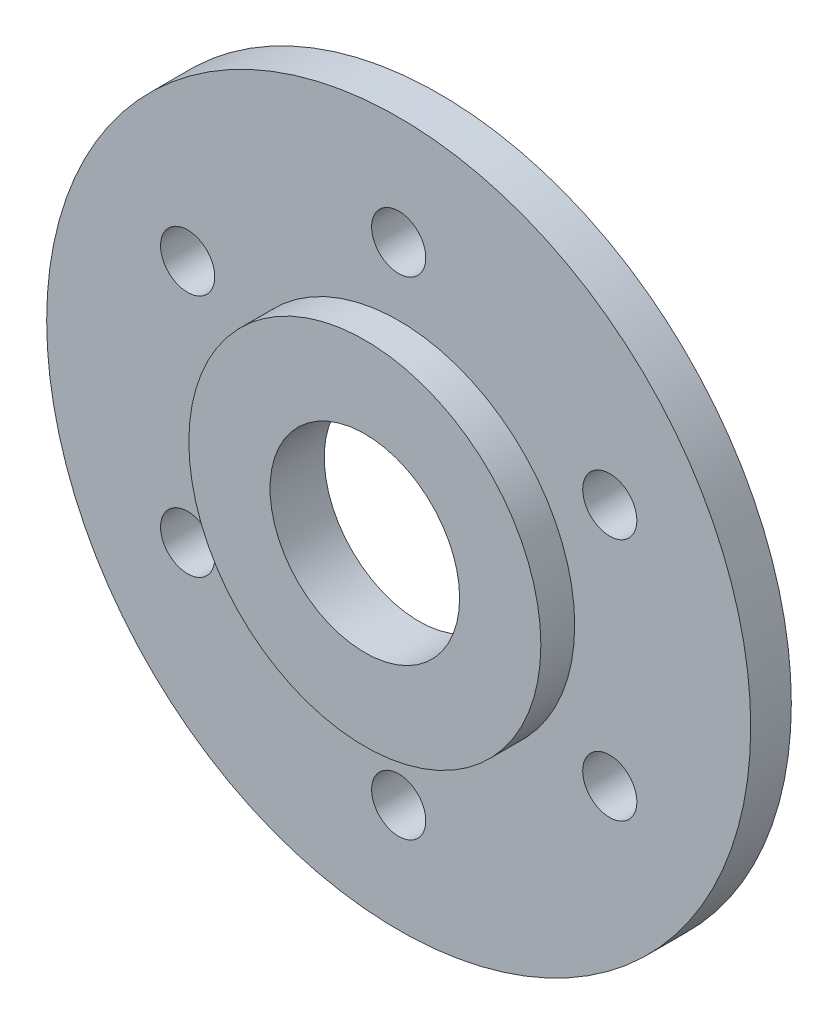
SolidWorks part; units mm, degrees
material "Resina de melamina"
ref_plane "Alzado" through (0, 0, 0) normal (0, 0, 1) x (1, 0, 0)
ref_plane "Planta" through (0, 0, 0) normal (0, 1, 0) x (1, 0, 0)
ref_plane "Vista lateral" through (0, 0, 0) normal (1, 0, 0) x (0, 0, -1)
sketch "Croquis1" plane through (0, 0, 0) normal (0, 0, 1) x (1, 0, 0)
  circle A0 centre (0, 0) radius 7
  circle A1 centre (0, 0) radius 13
  dimension "D1" = 14
  dimension "D2" = 26
extrude "Saliente-Extruir1" add sketch "Croquis1" along normal blind 4
sketch "Croquis2" plane through (0, 0, 0) normal (0, 0, -1) x (-1, 0, 0)
  circle A1 centre (0, 0) radius 26
  circle A2 centre (0, 0) radius 11.25
  dimension "D1" = 52
  dimension "D2" = 22.5
extrude "Saliente-Extruir2" add sketch "Croquis2" against normal mid plane 3 separate body
sketch "Croquis3" plane through (0, 0, -1.5) normal (0, 0, -1) x (-1, 0, 0)
  line L0 (0, 0) -> (0, 18) construction
  line L1 (0, 18) -> (0, 26) construction
  line L2 (0, 18) -> (0, 18.876) construction
  circle A0 centre (0, 18) radius 2
  circle A1 centre (0, 0) radius 26 construction
  circle A2 centre (15.5885, 9) radius 2
  circle A3 centre (15.5885, -9) radius 2
  circle A4 centre (0, -18) radius 2
  circle A5 centre (-15.5885, -9) radius 2
  circle A6 centre (-15.5885, 9) radius 2
  dimension "D3" = 4
  dimension "D1" = 18
  dimension "D2" = 6
extrude "Cortar-Extruir1" cut sketch "Croquis3" against normal through all
